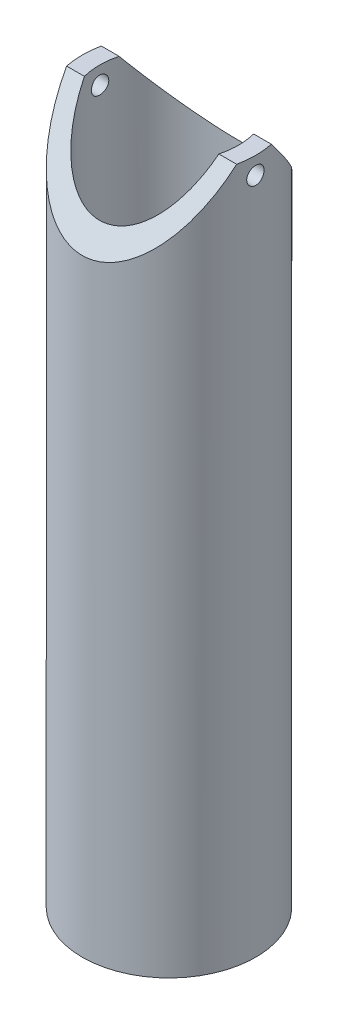
SolidWorks part; units mm, degrees
material "6061 Alloy"
ref_plane "Front Plane" through (0, 0, 0) normal (0, 0, 1) x (1, 0, 0)
ref_plane "Top Plane" through (0, 0, 0) normal (0, 1, 0) x (1, 0, 0)
ref_plane "Right Plane" through (0, 0, 0) normal (1, 0, 0) x (0, 0, -1)
sketch "Sketch1" plane through (0, 0, 0) normal (0, 1, 0) x (1, 0, 0)
  circle A0 centre (0, 0) radius 20
  circle A1 centre (0, 0) radius 25
  dimension "D1" = 5
  dimension "D2" = 50
extrude "Boss-Extrude1" add sketch "Sketch1" along normal blind 200
sketch "Sketch2" plane through (0, 0, 0) normal (1, 0, 0) x (0, 0, -1)
  line L0 (25, 175) -> (5, 200)
  line L1 (25, 0) -> (25, 200) construction
  line L2 (20, 200) -> (-20, 200) construction
  line L3 (5, 200) -> (-5, 200)
  line L4 (25, 200) -> (-25, 200) construction
  line L5 (-5, 200) -> (-25, 175)
  line L6 (-25, 200) -> (-25, 0) construction
  line L7 (-25, 175) -> (-25, 205.9373)
  line L8 (-25, 205.9373) -> (25, 205.9373)
  line L9 (25, 205.9373) -> (25, 175)
  line L10 (-25, 175) -> (25, 175) construction
  line L11 (0, 175) -> (0, 200) construction
  circle A0 centre (0, 195) radius 2.5
  dimension "D3" = 5
  dimension "D1" = 25
  dimension "D2" = 10
  dimension "D4" = 5
extrude "Cut-Extrude1" cut sketch "Sketch2" against normal blind 200 and the other way blind 200
